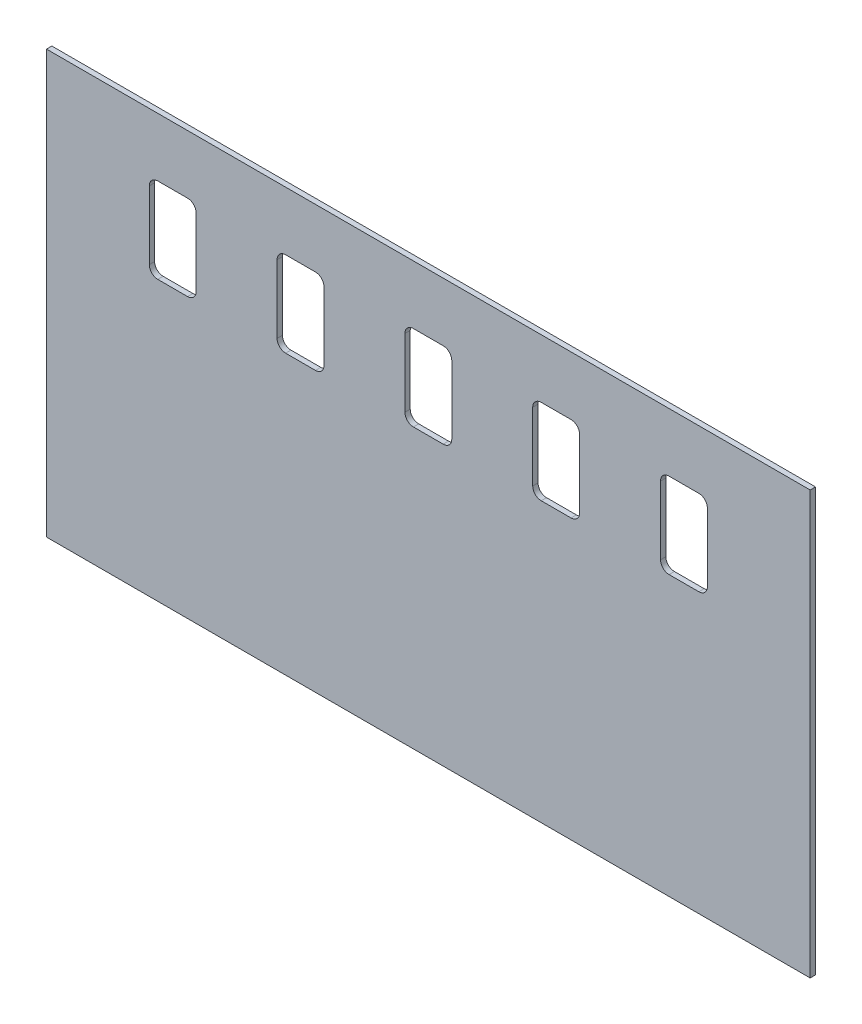
SolidWorks part; units mm, degrees
ref_plane "Front Plane" through (0, 0, 0) normal (0, 0, 1) x (1, 0, 0)
ref_plane "Top Plane" through (0, 0, 0) normal (0, 1, 0) x (1, 0, 0)
ref_plane "Right Plane" through (0, 0, 0) normal (1, 0, 0) x (0, 0, -1)
sketch "Sketch1" plane through (0, 0, 0) normal (0, 0, 1) x (1, 0, 0)
  line L1 (-227.6475, -125.984) -> (227.6475, -125.984)
  line L2 (-227.6475, -125.984) -> (-227.6475, 125.984)
  line L3 (-227.6475, 125.984) -> (227.6475, 125.984)
  line L4 (227.6475, -125.984) -> (227.6475, 125.984)
  line L5 (0, 125.984) -> (0, -125.984) construction
  line L6 (-227.6475, 0) -> (227.6475, 0) construction
  point P0 (0, 0)
  point P4 (-159.0675, 0)
  point P5 (159.0675, 0)
  point P6 (0, 88.1888)
  point P7 (0, -88.1888)
  dimension "Width" = 251.968
  dimension "Break" = 68.58
  dimension "D2" = 68.58
  dimension "D1" = 37.7952
  dimension "D3" = 37.7952
  dimension "D4" = 455.295
sketch "Sketch2" plane through (0, 0, 0) normal (1, 0, 0) x (0, 0, -1)
  line L0 (-1.5875, -125.984) -> (1.5875, -125.984)
  dimension "Thickness" = 3.175
sketch "Sketch3" plane through (0, 0, 0) normal (0, 0, 1) x (1, 0, 0)
  line L0 (-227.6475, -125.984) -> (-227.6475, 125.984) construction
  line L1 (-227.6475, -125.984) -> (227.6475, -125.984) construction
  line L2 (227.6475, -125.984) -> (227.6475, 125.984) construction
  line L3 (-227.6475, 125.984) -> (227.6475, 125.984) construction
  line L4 (-227.6475, -125.984) -> (-227.6475, 125.984)
  line L5 (-227.6475, -125.984) -> (227.6475, -125.984)
  line L6 (227.6475, -125.984) -> (227.6475, 125.984)
  line L7 (-227.6475, 125.984) -> (227.6475, 125.984)
extrude "Boss-Extrude1" add sketch "Sketch3" along normal mid plane 3.175
sketch "Sketch4" plane through (0, 0, 1.5875) normal (0, 0, 1) x (1, 0, 0)
  line L0 (-227.6475, 65.659) -> (-158.75, 65.659) construction
  line L1 (-82.55, 65.659) -> (-82.55, 91.059) construction
  line L2 (-82.55, 91.059) -> (-90.17, 91.059) construction
  line L3 (-158.75, 65.659) -> (-158.75, 91.059) construction
  line L6 (-227.6475, -93.091) -> (-227.6475, 65.659) construction
  line L8 (-158.75, 65.659) -> (-82.55, 65.659) construction
  line L9 (-82.55, 65.659) -> (-6.35, 65.659) construction
  line L10 (-6.35, 65.659) -> (69.85, 65.659) construction
  line L11 (69.85, 65.659) -> (146.05, 65.659) construction
  line L12 (-82.55, 65.659) -> (-82.55, 40.259) construction
  line L13 (-82.55, 40.259) -> (-62.23, 40.259) construction
  line L16 (-158.75, 91.059) -> (-166.37, 91.059) construction
  line L17 (-158.75, 65.659) -> (-158.75, 40.259) construction
  line L18 (-158.75, 40.259) -> (-138.43, 40.259) construction
  line L19 (-6.35, 65.659) -> (-6.35, 91.059) construction
  line L20 (-161.29, 91.059) -> (-143.51, 91.059)
  line L21 (-166.37, 85.979) -> (-166.37, 45.339)
  line L22 (-161.29, 40.259) -> (-143.51, 40.259)
  line L23 (-138.43, 85.979) -> (-138.43, 45.339)
  line L24 (-6.35, 91.059) -> (-13.97, 91.059) construction
  line L25 (-6.35, 65.659) -> (-6.35, 40.259) construction
  line L26 (-6.35, 40.259) -> (13.97, 40.259) construction
  line L27 (69.85, 65.659) -> (69.85, 91.059) construction
  line L28 (-8.89, 91.059) -> (8.89, 91.059)
  line L29 (-13.97, 85.979) -> (-13.97, 45.339)
  line L30 (-8.89, 40.259) -> (8.89, 40.259)
  line L31 (13.97, 85.979) -> (13.97, 45.339)
  line L32 (69.85, 91.059) -> (62.23, 91.059) construction
  line L33 (69.85, 65.659) -> (69.85, 40.259) construction
  line L34 (69.85, 40.259) -> (90.17, 40.259) construction
  line L35 (146.05, 65.659) -> (146.05, 91.059) construction
  line L36 (67.31, 91.059) -> (85.09, 91.059)
  line L37 (62.23, 85.979) -> (62.23, 45.339)
  line L38 (67.31, 40.259) -> (85.09, 40.259)
  line L39 (90.17, 85.979) -> (90.17, 45.339)
  line L40 (146.05, 91.059) -> (138.43, 91.059) construction
  line L41 (146.05, 65.659) -> (146.05, 40.259) construction
  line L42 (146.05, 40.259) -> (166.37, 40.259) construction
  line L43 (-227.6475, 125.984) -> (-227.6475, -125.984) construction
  line L44 (143.51, 91.059) -> (161.29, 91.059)
  line L45 (138.43, 85.979) -> (138.43, 45.339)
  line L46 (143.51, 40.259) -> (161.29, 40.259)
  line L47 (166.37, 85.979) -> (166.37, 45.339)
  line L48 (-85.09, 91.059) -> (-67.31, 91.059)
  line L49 (-90.17, 85.979) -> (-90.17, 45.339)
  line L50 (-85.09, 40.259) -> (-67.31, 40.259)
  line L51 (-62.23, 85.979) -> (-62.23, 45.339)
  arc A0 (138.43, 45.339) -> (143.51, 40.259) centre (143.51, 45.339) ccw
  arc A1 (166.37, 45.339) -> (161.29, 40.259) centre (161.29, 45.339) cw
  arc A2 (161.29, 91.059) -> (166.37, 85.979) centre (161.29, 85.979) cw
  arc A3 (138.43, 85.979) -> (143.51, 91.059) centre (143.51, 85.979) cw
  arc A4 (62.23, 45.339) -> (67.31, 40.259) centre (67.31, 45.339) ccw
  arc A5 (90.17, 45.339) -> (85.09, 40.259) centre (85.09, 45.339) cw
  arc A6 (85.09, 91.059) -> (90.17, 85.979) centre (85.09, 85.979) cw
  arc A7 (67.31, 91.059) -> (62.23, 85.979) centre (67.31, 85.979) ccw
  arc A8 (-13.97, 45.339) -> (-8.89, 40.259) centre (-8.89, 45.339) ccw
  arc A9 (13.97, 45.339) -> (8.89, 40.259) centre (8.89, 45.339) cw
  arc A10 (8.89, 91.059) -> (13.97, 85.979) centre (8.89, 85.979) cw
  arc A11 (-8.89, 91.059) -> (-13.97, 85.979) centre (-8.89, 85.979) ccw
  arc A15 (-138.43, 45.339) -> (-143.51, 40.259) centre (-143.51, 45.339) cw
  arc A16 (-143.51, 91.059) -> (-138.43, 85.979) centre (-143.51, 85.979) cw
  arc A17 (-166.37, 85.979) -> (-161.29, 91.059) centre (-161.29, 85.979) cw
  arc A18 (-166.37, 45.339) -> (-161.29, 40.259) centre (-161.29, 45.339) ccw
  arc A19 (-90.17, 45.339) -> (-85.09, 40.259) centre (-85.09, 45.339) ccw
  arc A20 (-62.23, 45.339) -> (-67.31, 40.259) centre (-67.31, 45.339) cw
  arc A21 (-67.31, 91.059) -> (-62.23, 85.979) centre (-67.31, 85.979) cw
  arc A22 (-85.09, 91.059) -> (-90.17, 85.979) centre (-85.09, 85.979) ccw
  point P4 (0, 0)
  point P5 (0, 0)
  point P14 (-152.4, 91.059)
  point P15 (-227.6475, 65.659)
  point P16 (-76.2, 91.059)
  point P17 (-90.17, 65.659)
  point P18 (-13.97, 65.659)
  point P95 (62.23, 65.659)
  point P96 (138.43, 65.659)
  point P97 (0, 91.059)
  point P98 (76.2, 91.059)
  point P99 (152.4, 91.059)
  point P100 (0, 0)
  point P103 (0, 0)
  dimension "D1" = 5.08
  dimension "D2" = 5.08
  dimension "D8" = 27.94
  dimension "D9" = 27.94
  dimension "D10" = 27.94
  dimension "D11" = 27.94
  dimension "D12" = 27.94
  dimension "D3" = 76.2
  dimension "D4" = 76.2
  dimension "D5" = 152.4
  dimension "D6" = 152.4
  dimension "D13" = 25.4
  dimension "D14" = 25.4
extrude "Cut-Extrude1" cut sketch "Sketch4" against normal blind 25.4 contours L21 A18 L22 A15 L23 A16 L20 A17 | A22 L48 A21 L51 A20 L50 A19 L49 | L29 A8 L30 A9 L31 A10 L28 A11 | L37 A4 L38 A5 L39 A6 L36 A7 | A3 L44 A2 L47 A1 L46 A0 L45
equation "\"D1@Boss-Extrude1\" = \"Thickness@Sketch2\""
equation "\"D2@Sketch1\" = \"Break@Sketch1\""
equation "\"D1@Sketch1\"=\"Width@Sketch1\"*0.15"
equation "\"D3@Sketch1\"=\"D1@Sketch1\""
equation "\"SlotWidth\"= 1.1in"
equation "\"D8@Sketch4\"=\"SlotWidth\""
equation "\"D9@Sketch4\"=\"SlotWidth\""
equation "\"D10@Sketch4\"=\"SlotWidth\""
equation "\"D11@Sketch4\"=\"SlotWidth\""
equation "\"D12@Sketch4\"=\"SlotWidth\""
